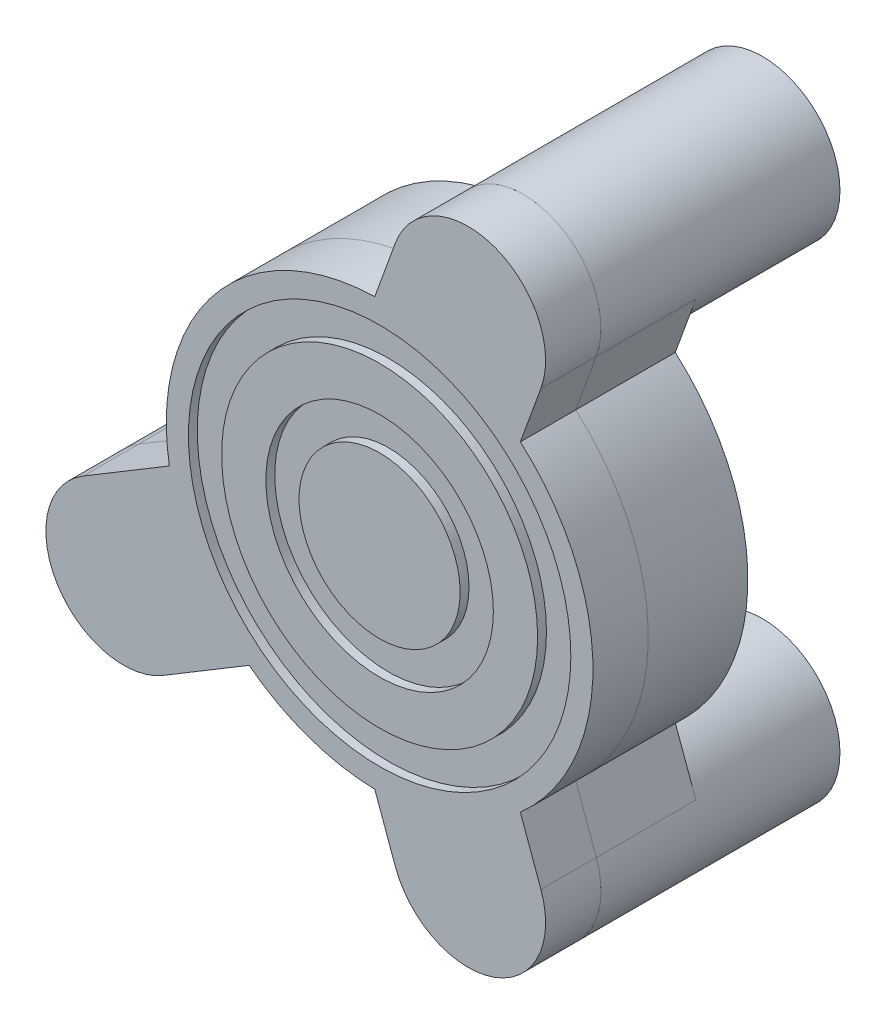
SolidWorks part; units mm, degrees
ref_plane "Front Plane" through (0, 0, 0) normal (0, 0, 1) x (1, 0, 0)
ref_plane "Top Plane" through (0, 0, 0) normal (0, 1, 0) x (1, 0, 0)
ref_plane "Right Plane" through (0, 0, 0) normal (1, 0, 0) x (0, 0, -1)
sketch "Sketch1" plane through (0, 0, 0) normal (0, 0, 1) x (1, 0, 0)
  line L4 (-5.5, 6) -> (-5.5, -6)
  line L5 (-5.5, -6) -> (5.5, -6)
  line L6 (5.5, -6) -> (5.5, 6)
  line L7 (5.5, 6) -> (-5.5, 6)
  line L8 (-5.5, 6) -> (-5.5, -6)
  line L9 (-5.5, -6) -> (5.5, -6)
  line L10 (5.5, -6) -> (5.5, 6)
  line L11 (5.5, 6) -> (-5.5, 6)
  circle A0 centre (0, 0) radius 9.6394
  dimension "D2" = 1.5
  dimension "D1" = 0
extrude "Boss-Extrude1" add sketch "Sketch1" against normal blind 2.5
sketch "Sketch2" plane through (0, 0, 0) normal (0, 0, 1) x (1, 0, 0)
  line L0 (-3.81, 3.81) -> (-3.81, -3.81) construction
  line L1 (3.81, 3.81) -> (3.81, -3.81) construction
  line L3 (-5.16, -5.5) -> (-2.46, -5.5)
  line L4 (-5.16, -5.5) -> (-5.16, 5.5)
  line L5 (-5.16, 5.5) -> (-2.46, 5.5)
  line L6 (-2.46, -5.5) -> (-2.46, 5.5)
  line L7 (-5.16, -5.5) -> (-2.46, 5.5) construction
  line L8 (-5.16, 5.5) -> (-2.46, -5.5) construction
  line L9 (2.46, -5.5) -> (5.16, -5.5)
  line L10 (2.46, -5.5) -> (2.46, 5.5)
  line L11 (2.46, 5.5) -> (5.16, 5.5)
  line L12 (5.16, -5.5) -> (5.16, 5.5)
  line L13 (2.46, -5.5) -> (5.16, 5.5) construction
  line L14 (2.46, 5.5) -> (5.16, -5.5) construction
  circle A0 centre (3.81, -3.81) radius 0.4 construction
  circle A1 centre (0, 0) radius 9.6394
  circle A2 centre (0, 0) radius 9.6394
  circle A3 centre (3.81, -3.81) radius 0.4
  circle A4 centre (-3.81, -3.81) radius 0.4 construction
  circle A5 centre (-3.81, -3.81) radius 0.4
  circle A6 centre (-3.81, 3.81) radius 0.4 construction
  circle A7 centre (-3.81, 3.81) radius 0.4
  circle A8 centre (3.81, 3.81) radius 0.4 construction
  circle A9 centre (3.81, 3.81) radius 0.4
  point P15 (-3.81, 0)
  point P20 (3.81, 0)
  line M3 (-5.5, 6) -> (5.5, 6)
  line M4 (5.5, 6) -> (5.5, -6)
  line M5 (5.5, -6) -> (-5.5, -6)
  line M6 (-5.5, -6) -> (-5.5, 6)
  circle M7 centre (0, 0) radius 9.6394
  dimension "D2" = 2.7
  dimension "D3" = 11
  dimension "D1" = 0
extrude "Boss-Extrude2" add sketch "Sketch2" along normal blind 2 contours L12 L9 L10 L11 L6 L3 L4 L5 M3 M6 M5 M4 | M7 M6 M3 M4 M5 region at (-9.3668, 0, 0) region at (0, 0, 0)
sketch "Sketch3" plane through (0, 0, 2) normal (0, 0, 1) x (1, 0, 0)
  line L0 (0, 0) -> (4, 11) construction
  line L1 (0, 0) -> (4, -11) construction
  line L2 (0, 0) -> (-11.5786, -6.9596) construction
  line L3 (-2.3941, -6.5778) -> (-12.2609, -2.9866) construction
  line L4 (-15.6819, -8) -> (-14.8675, -5.7625) construction
  line L5 (-13.3817, -3.9598) -> (-9.5011, -1.6272)
  line L6 (-9.7755, -9.9594) -> (-5.8949, -7.6269)
  line L8 (0.7107, -12.1961) -> (-0.2199, -9.6369)
  line L9 (7.2893, -9.8039) -> (6.3587, -7.2447)
  line L10 (7.2893, 9.8039) -> (6.3587, 7.2447)
  line L11 (0.7107, 12.1961) -> (-0.2199, 9.6369)
  circle A0 centre (-11.5786, -6.9596) radius 1
  circle A1 centre (4, -11) radius 1 construction
  circle A2 centre (4, -11) radius 1
  circle A3 centre (4, 11) radius 1 construction
  circle A4 centre (4, 11) radius 1
  circle A5 centre (4, 11) radius 3.5
  circle A6 centre (4, -11) radius 3.5
  circle A7 centre (-11.5786, -6.9596) radius 3.5
  circle A8 centre (0, 0) radius 9.6394 construction
  circle M24 centre (0, 0) radius 9.6394
  dimension "D1" = 7
extrude "Boss-Extrude3" add sketch "Sketch3" against normal up to surface (4.5 mm away) contours A7 A0 | A7 L6 L5 M24 | A6 A2 M24 | A6 L8 M24 | A6 L9 M24 | A5 L10 M24 | A5 L11 M24 | A5 A4 M24 region at (-11.3837, -2.8895, 2) region at (-9.9041, -3.9994, 2) region at (0.3163, 10.2795, 2) region at (4.5905, 14.352, 2) region at (0.3163, -10.2795, 2) region at (6.3605, 8.0816, 2) region at (0.598, -10.897, 2) region at (6.3605, -8.0816, 2) up to face at (0, 0, -2.5)
sketch "Sketch4" plane through (0, 0, -2.5) normal (0, 0, -1) x (-1, 0, 0)
  line L6 (5.8949, -7.6269) -> (9.7755, -9.9594)
  line L7 (13.3817, -3.9598) -> (9.5011, -1.6272)
  line L8 (0.2199, 9.6369) -> (-0.7107, 12.1961)
  line L9 (-7.2893, 9.8039) -> (-6.3587, 7.2447)
  line L10 (-6.3587, -7.2447) -> (-7.2893, -9.8039)
  line L11 (-0.7107, -12.1961) -> (0.2199, -9.6369)
  line L13 (13.3817, -3.9598) -> (9.5011, -1.6272)
  line L14 (0.2199, 9.6369) -> (-0.7107, 12.1961)
  line L17 (-0.7107, -12.1961) -> (0.2199, -9.6369)
  circle A0 centre (-4, -11) radius 1 construction
  circle A1 centre (-4, -11) radius 1
  circle A2 centre (11.5786, -6.9596) radius 1 construction
  circle A3 centre (11.5786, -6.9596) radius 1
  circle A4 centre (-4, 11) radius 1 construction
  circle A5 centre (-4, 11) radius 1
  arc A6 (0.2199, -9.6369) -> (5.8949, -7.6269) centre (0, 0) ccw
  arc A7 (9.7755, -9.9594) -> (13.3817, -3.9598) centre (11.5786, -6.9596) ccw
  arc A8 (9.5011, -1.6272) -> (0.2199, 9.6369) centre (0, 0) ccw
  arc A9 (-0.7107, 12.1961) -> (-7.2893, 9.8039) centre (-4, 11) ccw
  arc A10 (-6.3587, 7.2447) -> (-6.3587, -7.2447) centre (0, 0) ccw
  arc A11 (-7.2893, -9.8039) -> (-0.7107, -12.1961) centre (-4, -11) ccw
  arc A12 (0.2199, -9.6369) -> (5.8949, -7.6269) centre (0, 0) ccw
  circle A13 centre (11.5786, -6.9596) radius 3.5
  arc A14 (9.5011, -1.6272) -> (0.2199, 9.6369) centre (0, 0) ccw
  circle A15 centre (-4, 11) radius 3.5
  arc A16 (-6.3587, 7.2447) -> (-6.3587, -7.2447) centre (0, 0) ccw
  circle A17 centre (-4, -11) radius 3.5
  arc M19 (9.7755, -9.9594) -> (13.3817, -3.9598) centre (11.5786, -6.9596) ccw
  arc M23 (-0.7107, 12.1961) -> (-7.2893, 9.8039) centre (-4, 11) ccw
  arc M27 (-7.2893, -9.8039) -> (-0.7107, -12.1961) centre (-4, -11) ccw
  circle M29 centre (11.5786, -6.9596) radius 1
  circle M30 centre (-4, -11) radius 1
  circle M31 centre (-4, 11) radius 1
  dimension "D1" = 0
extrude "Boss-Extrude4" add sketch "Sketch4" along normal up to surface (6.3 mm away) contours A13 M19 M29 | A17 M27 M30 | A15 M23 M31 region at (-8.6636, -5.2075, -2.5) region at (5.1623, -14.1962, -2.5) region at (0.6506, 11.5901, -2.5)
sketch "Sketch5" plane through (0, 0, -2.5) normal (0, 0, -1) x (-1, 0, 0)
  line L0 (0, 6) -> (0, -6) construction
  line L1 (-5.5, 6) -> (5.5, 6) construction
  line L2 (5.5, -6) -> (-5.5, -6) construction
  line L3 (5.5, -6) -> (-5.5, -6)
  line L4 (-5.5, 6) -> (5.5, 6)
  line L6 (-2, 4) -> (2, 4)
  line L7 (-2, 4) -> (-2, 8)
  line L8 (-2, 8) -> (2, 8)
  line L9 (2, 4) -> (2, 8)
  line L10 (-2, 4) -> (2, 8) construction
  line L11 (-2, 8) -> (2, 4) construction
  line L12 (-2, -4) -> (2, -4)
  line L13 (-2, -4) -> (-2, -8)
  line L14 (-2, -8) -> (2, -8)
  line L15 (2, -4) -> (2, -8)
  line L16 (-2, -4) -> (2, -8) construction
  line L17 (-2, -8) -> (2, -4) construction
  dimension "D1" = 4
  dimension "D2" = 4
extrude "Boss-Extrude5" add sketch "Sketch5" along normal blind 1.5 contours L15 L3 L13 L14 | L4 L9 L8 L7 region at (0, -7, -2.5) region at (0, 7, -2.5)
fillet "Fillet1" radius 1.5 6 edges at (0, 8, -4) (0, -8, -4) (2, -7, -4) (-2, -7, -4) (-2, 7, -4) (2, 7, -4)
sketch "Sketch6" plane through (0, 0, 2) normal (0, 0, 1) x (1, 0, 0)
  circle A0 centre (4, 11) radius 2.05
  circle A1 centre (-11.5786, -6.9596) radius 2.05
  circle A2 centre (4, -11) radius 2.05
  dimension "D1" = 4.1
extrude "Cut-Extrude1" cut sketch "Sketch6" against normal offset from surface (6.8 mm away) 4 up to face at (-12.5786, -6.9596, -8.8)
sketch "Sketch7" plane through (0, 0, -4.8) normal (0, 0, 1) x (1, 0, 0)
  circle A0 centre (-11.5786, -6.9596) radius 1 construction
  circle A1 centre (-11.5786, -6.9596) radius 1
  circle A2 centre (4, 11) radius 1 construction
  circle A3 centre (4, 11) radius 1
  circle A4 centre (4, -11) radius 1 construction
  circle A5 centre (4, -11) radius 1
extrude "Boss-Extrude6" add sketch "Sketch7" against normal blind 0.2
sketch "Sketch8" plane through (0, 0, 2) normal (0, 0, 1) x (1, 0, 0)
  line L0 (-2.46, 5.5) -> (0, 0)
  line L1 (0, 0) -> (2.46, 5.5)
  line L2 (2.46, -5.5) -> (-0.2199, -9.6369)
  line L3 (-2.46, -5.5) -> (-4.4397, -8.5561)
  line L4 (-2.46, -5.5) -> (-2.46, 5.5) construction
  line L5 (-2.46, -5.5) -> (-2.46, 5.5)
  line L6 (2.46, -5.5) -> (2.46, 5.5) construction
  line L7 (2.46, -5.5) -> (2.46, 5.5)
  arc A0 (-5.8949, -7.6269) -> (-0.2199, -9.6369) centre (0, 0) ccw construction
  arc A1 (-4.4397, -8.5561) -> (-0.2199, -9.6369) centre (0, 0) ccw
  dimension "D1" = 4.1293
extrude "Cut-Extrude2" cut sketch "Sketch8" against normal blind 1
fillet "Fillet2" radius 1 3 edges at (2.46, -5.5, 1.5) (-2.46, -5.5, 1.5) (0, 0, 1.5)
fillet "Fillet3" radius 1 1 edges at (-2.3917, -9.338, 1)
sketch "Sketch9" plane through (0, 0, 2) normal (0, 0, 1) x (1, 0, 0)
  line L0 (0.7199, -9.2952) -> (1.6505, -11.8544)
  line L1 (6.3495, -10.1456) -> (5.1756, -6.9175)
  line L2 (5.1756, 6.9175) -> (6.3495, 10.1456)
  line L3 (1.6505, 11.8544) -> (0.4767, 8.6263)
  line L4 (-8.3759, -2.1177) -> (-12.8665, -4.8169)
  line L5 (-10.2907, -9.1023) -> (-6.41, -6.7698)
  line L6 (-6.41, -6.7698) -> (-5.8949, -7.6269)
  line L7 (-0.2199, -9.6369) -> (0.7199, -9.2952)
  line L16 (5.16, -5.5) -> (3.0037, -5.5)
  line L17 (2.1644, -5.9563) -> (-0.2199, -9.6369)
  line L18 (-0.2199, -9.6369) -> (0.7107, -12.1961)
  line L19 (7.2893, -9.8039) -> (6.3587, -7.2447)
  line L20 (6.3587, 7.2447) -> (7.2893, 9.8039)
  line L21 (0.7107, 12.1961) -> (-0.2199, 9.6369)
  line L22 (-9.5011, -1.6272) -> (-13.3817, -3.9598)
  line L23 (-9.7755, -9.9594) -> (-5.8949, -7.6269)
  line L24 (-4.4397, -8.5561) -> (-3.46, -7.0437)
  line L25 (-4.2993, -5.5) -> (-5.16, -5.5)
  line L26 (-5.16, -5.5) -> (-5.16, 5.5)
  line L27 (-5.16, 5.5) -> (-2.46, 5.5)
  line L28 (-2.46, 5.5) -> (-0.9129, 2.0409)
  line L29 (0.9129, 2.0409) -> (2.46, 5.5)
  line L30 (2.46, 5.5) -> (5.16, 5.5)
  line L31 (5.16, 5.5) -> (5.16, -5.5)
  line L34 (-0.2199, -9.6369) -> (0.7107, -12.1961)
  line L35 (7.2893, -9.8039) -> (6.3587, -7.2447)
  line L36 (6.3587, 7.2447) -> (7.2893, 9.8039)
  line L37 (0.7107, 12.1961) -> (-0.2199, 9.6369)
  line L38 (-9.5011, -1.6272) -> (-13.3817, -3.9598)
  line L39 (-9.7755, -9.9594) -> (-5.8949, -7.6269)
  arc A0 (1.6505, -11.8544) -> (6.3495, -10.1456) centre (4, -11) ccw
  arc A1 (5.1756, -6.9175) -> (5.1756, 6.9175) centre (0, 0) ccw
  arc A2 (6.3495, 10.1456) -> (1.6505, 11.8544) centre (4, 11) ccw
  arc A3 (0.4767, 8.6263) -> (-8.3759, -2.1177) centre (0, 0) ccw
  arc A4 (-12.8665, -4.8169) -> (-10.2907, -9.1023) centre (-11.5786, -6.9596) ccw
  circle A5 centre (-11.5786, -6.9596) radius 3.5
  circle A6 centre (4, 11) radius 3.5
  circle A7 centre (4, -11) radius 3.5
  arc A9 (3.0037, -5.5) -> (2.1644, -5.9563) centre (3.0037, -6.5) ccw
  arc A10 (0.7107, -12.1961) -> (7.2893, -9.8039) centre (4, -11) ccw
  arc A11 (6.3587, -7.2447) -> (6.3587, 7.2447) centre (0, 0) ccw
  arc A12 (7.2893, 9.8039) -> (0.7107, 12.1961) centre (4, 11) ccw
  arc A13 (-0.2199, 9.6369) -> (-9.5011, -1.6272) centre (0, 0) ccw
  arc A14 (-13.3817, -3.9598) -> (-9.7755, -9.9594) centre (-11.5786, -6.9596) ccw
  arc A15 (-5.8949, -7.6269) -> (-4.4397, -8.5561) centre (0, 0) ccw
  arc A16 (-3.46, -7.0437) -> (-4.2993, -5.5) centre (-4.2993, -6.5) ccw
  arc A17 (-0.9129, 2.0409) -> (0.9129, 2.0409) centre (0, 2.4492) ccw
  arc A19 (0.7107, -12.1961) -> (7.2893, -9.8039) centre (4, -11) ccw
  arc A20 (6.3587, -7.2447) -> (6.3587, 7.2447) centre (0, 0) ccw
  arc A21 (7.2893, 9.8039) -> (0.7107, 12.1961) centre (4, 11) ccw
  arc A22 (-0.2199, 9.6369) -> (-9.5011, -1.6272) centre (0, 0) ccw
  arc A23 (-13.3817, -3.9598) -> (-9.7755, -9.9594) centre (-11.5786, -6.9596) ccw
  line M29 (-0.2199, -9.6369) -> (0.7107, -12.1961)
  arc M30 (0.7107, -12.1961) -> (7.2893, -9.8039) centre (4, -11) ccw
  line M31 (7.2893, -9.8039) -> (6.3587, -7.2447)
  arc M32 (6.3587, -7.2447) -> (6.3587, 7.2447) centre (0, 0) ccw
  line M33 (6.3587, 7.2447) -> (7.2893, 9.8039)
  arc M34 (7.2893, 9.8039) -> (0.7107, 12.1961) centre (4, 11) ccw
  line M35 (0.7107, 12.1961) -> (-0.2199, 9.6369)
  arc M36 (-0.2199, 9.6369) -> (-9.5011, -1.6272) centre (0, 0) ccw
  line M37 (-9.5011, -1.6272) -> (-13.3817, -3.9598)
  arc M38 (-13.3817, -3.9598) -> (-9.7755, -9.9594) centre (-11.5786, -6.9596) ccw
  line M39 (-9.7755, -9.9594) -> (-5.8949, -7.6269)
  circle M51 centre (4, 11) radius 2.05
  circle M52 centre (-11.5786, -6.9596) radius 2.05
  circle M53 centre (4, -11) radius 2.05
  dimension "D1" = 0
  dimension "D2" = 1
extrude "Boss-Extrude7" add sketch "Sketch9" along normal blind 1.5 separate body contours L3 A6 L2 A2 M51 | A6 L3 A2 L2 M34 | L4 A5 L5 A4 M38 | L5 A5 L4 A4 M52 | A6 A5 L4 A3 L3 M35 M36 M37 | A5 L6 L5 M39 | A7 L0 L7 M29 | A7 L1 A0 L0 M30 | L1 A7 L0 A0 M53 | A7 A6 L2 A1 L1 M31 M32 M33 | M52 | M51 | M53 region at (0.3358, -10.1524, 2) region at (2.8321, -7.7884, 2) region at (1.1412, -10.7364, 2) region at (5.533, -7.3119, 2) region at (2.8321, 7.7884, 2) region at (6.0217, 8.9616, 2) region at (0.4429, 9.1628, 2) region at (-8.8978, -4.8427, 2) region at (-11.8674, -4.1018, 2) region at (-7.39, -8.0077, 2) region at (4, 11, 2) region at (-11.5786, -6.9596, 2) region at (4, -11, 2)
sketch "Sketch10" plane through (0, 0, 3.5) normal (0, 0, 1) x (1, 0, 0)
  line L14 (-9.7755, -9.9594) -> (-5.8949, -7.6269)
  line L15 (-5.8949, -7.6269) -> (-6.41, -6.7698)
  line L16 (-6.41, -6.7698) -> (-8.1912, -7.8404)
  line L17 (-10.7671, -3.555) -> (-8.3759, -2.1177)
  line L18 (0.4767, 8.6263) -> (0.8134, 9.5523)
  line L19 (5.5124, 7.8436) -> (5.1756, 6.9175)
  line L20 (5.1756, -6.9175) -> (5.5124, -7.8436)
  line L21 (0.8134, -9.5523) -> (0.7199, -9.2952)
  line L22 (0.7199, -9.2952) -> (-0.2199, -9.6369)
  line L23 (-0.2199, -9.6369) -> (0.7107, -12.1961)
  line L24 (7.2893, -9.8039) -> (6.3587, -7.2447)
  line L25 (6.3587, 7.2447) -> (7.2893, 9.8039)
  line L26 (0.7107, 12.1961) -> (-0.2199, 9.6369)
  line L27 (-9.5011, -1.6272) -> (-13.3817, -3.9598)
  line L28 (-9.7755, -9.9594) -> (-5.8949, -7.6269)
  line L34 (5.1756, -6.9175) -> (5.5124, -7.8436)
  line L35 (0.8134, -9.5523) -> (0.7199, -9.2952)
  line L36 (0.7199, -9.2952) -> (-0.2199, -9.6369)
  line L37 (-0.2199, -9.6369) -> (0.7107, -12.1961)
  line L38 (7.2893, -9.8039) -> (6.3587, -7.2447)
  line L39 (6.3587, 7.2447) -> (7.2893, 9.8039)
  line L40 (0.7107, 12.1961) -> (-0.2199, 9.6369)
  line L41 (-9.5011, -1.6272) -> (-13.3817, -3.9598)
  arc A0 (-5.8949, -7.6269) -> (-4.4397, -8.5561) centre (0, 0) ccw construction
  arc A1 (-5.8949, -7.6269) -> (-0.2199, -9.6369) centre (0, 0) ccw
  arc A10 (-13.3817, -3.9598) -> (-9.7755, -9.9594) centre (-11.5786, -6.9596) ccw
  arc A11 (-8.1912, -7.8404) -> (-10.7671, -3.555) centre (-11.5786, -6.9596) ccw
  arc A12 (0.4767, 8.6263) -> (-8.3759, -2.1177) centre (0, 0) ccw
  arc A13 (0.8134, 9.5523) -> (5.5124, 7.8436) centre (4, 11) ccw
  arc A14 (5.1756, -6.9175) -> (5.1756, 6.9175) centre (0, 0) ccw
  arc A15 (5.5124, -7.8436) -> (0.8134, -9.5523) centre (4, -11) ccw
  arc A16 (0.7107, -12.1961) -> (7.2893, -9.8039) centre (4, -11) ccw
  arc A17 (6.3587, -7.2447) -> (6.3587, 7.2447) centre (0, 0) ccw
  arc A18 (7.2893, 9.8039) -> (0.7107, 12.1961) centre (4, 11) ccw
  arc A19 (-0.2199, 9.6369) -> (-9.5011, -1.6272) centre (0, 0) ccw
  arc A20 (-13.3817, -3.9598) -> (-9.7755, -9.9594) centre (-11.5786, -6.9596) ccw
  arc A25 (5.5124, -7.8436) -> (0.8134, -9.5523) centre (4, -11) ccw
  arc A26 (0.7107, -12.1961) -> (7.2893, -9.8039) centre (4, -11) ccw
  arc A27 (6.3587, -7.2447) -> (6.3587, 7.2447) centre (0, 0) ccw
  arc A28 (7.2893, 9.8039) -> (0.7107, 12.1961) centre (4, 11) ccw
  arc A29 (-0.2199, 9.6369) -> (-9.5011, -1.6272) centre (0, 0) ccw
  point P9 (-0.415, -9.6305)
  arc M26 (-13.3817, -3.9598) -> (-9.7755, -9.9594) centre (-11.5786, -6.9596) ccw
  line M27 (-9.7755, -9.9594) -> (-5.8949, -7.6269)
  line M28 (-5.8949, -7.6269) -> (-6.41, -6.7698)
  line M29 (-6.41, -6.7698) -> (-8.1912, -7.8404)
  arc M30 (-8.1912, -7.8404) -> (-10.7671, -3.555) centre (-11.5786, -6.9596) ccw
  line M31 (-10.7671, -3.555) -> (-8.3759, -2.1177)
  arc M32 (-8.3759, -2.1177) -> (0.4767, 8.6263) centre (0, 0) cw
  line M33 (0.4767, 8.6263) -> (0.8134, 9.5523)
  arc M34 (0.8134, 9.5523) -> (5.5124, 7.8436) centre (4, 11) ccw
  line M35 (5.5124, 7.8436) -> (5.1756, 6.9175)
  arc M36 (5.1756, 6.9175) -> (5.1756, -6.9175) centre (0, 0) cw
  line M37 (5.1756, -6.9175) -> (5.5124, -7.8436)
  arc M38 (5.5124, -7.8436) -> (0.8134, -9.5523) centre (4, -11) ccw
  line M39 (0.8134, -9.5523) -> (0.7199, -9.2952)
  line M40 (0.7199, -9.2952) -> (-0.2199, -9.6369)
  line M41 (-0.2199, -9.6369) -> (0.7107, -12.1961)
  arc M42 (0.7107, -12.1961) -> (7.2893, -9.8039) centre (4, -11) ccw
  line M43 (7.2893, -9.8039) -> (6.3587, -7.2447)
  arc M44 (6.3587, -7.2447) -> (6.3587, 7.2447) centre (0, 0) ccw
  line M45 (6.3587, 7.2447) -> (7.2893, 9.8039)
  arc M46 (7.2893, 9.8039) -> (0.7107, 12.1961) centre (4, 11) ccw
  line M47 (0.7107, 12.1961) -> (-0.2199, 9.6369)
  arc M48 (-0.2199, 9.6369) -> (-9.5011, -1.6272) centre (0, 0) ccw
  line M49 (-9.5011, -1.6272) -> (-13.3817, -3.9598)
  dimension "D1" = 0
extrude "Boss-Extrude8" add sketch "Sketch10" along normal blind 1 contours A1 M28 M40 M39 M38 M37 M36 M35 M34 M33 M32 M31 M30 M29 | M49 M26 M27 M28 M29 M30 M31 M32 M33 M34 M35 M36 M37 M38 M39 M40 M41 M42 M43 M44 M45 M46 M47 M48 region at (-14.2518, -8.5664, 3.5) region at (-0.3764, -0.4166, 3.5)
sketch "Sketch11" plane through (0, 0, 2) normal (0, 0, -1) x (-1, 0, 0)
  circle A0 centre (-4, 11) radius 1.8
  circle A1 centre (11.5786, -6.9596) radius 1.8
  circle A2 centre (-4, -11) radius 1.8
  dimension "D1" = 3.6
extrude "Boss-Extrude9" add sketch "Sketch11" along normal blind 2 separate body
combine bodies "Combine1" operation type add bodies to combine 110 112 111 113
chamfer "Chamfer1" distance 0.8 angle 45 3 edges at (2.2, 11, 0) (-13.3786, -6.9596, 0) (2.2, -11, 0)
sketch "Sketch12" plane through (0, 0, 4.5) normal (0, 0, 1) x (1, 0, 0)
  circle A0 centre (0, 0) radius 3.6394
  circle A1 centre (0, 0) radius 5.1394
  circle A2 centre (0, 0) radius 7.1394
  circle A3 centre (0, 0) radius 8.6394
  arc A4 (-0.2199, 9.6369) -> (-9.5011, -1.6272) centre (0, 0) ccw construction
  dimension "D1" = 1
  dimension "D2" = 1.5
  dimension "D3" = 1.5
  dimension "D4" = 2
extrude "Cut-Extrude3" cut sketch "Sketch12" against normal blind 0.4 contours A3 A2 | A1 A0 region at (-4.994, 0, 4.5) region at (-8.3951, 0, 4.5)
